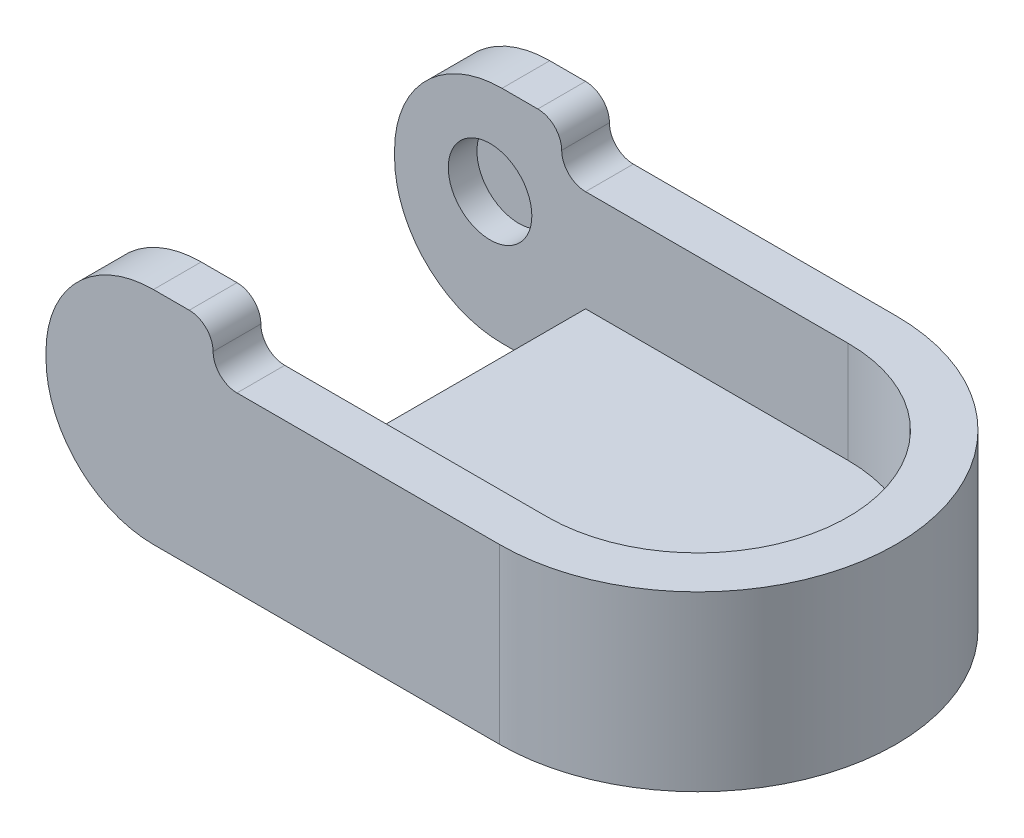
SolidWorks part; units mm, degrees
ref_plane "Front Plane" through (0, 0, 0) normal (0, 0, 1) x (1, 0, 0)
ref_plane "Top Plane" through (0, 0, 0) normal (0, 1, 0) x (1, 0, 0)
ref_plane "Right Plane" through (0, 0, 0) normal (1, 0, 0) x (0, 0, -1)
sketch "Sketch1" plane through (0, 0, 0) normal (0, 1, 0) x (1, 0, 0)
  line L0 (0, 0) -> (17, 0)
  line L1 (17, 16.6) -> (0, 16.6)
  line L2 (0, 16.6) -> (0, 14.6)
  line L3 (0, 14.6) -> (6, 14.6)
  line L4 (6, 14.6) -> (6, 2)
  line L5 (6, 2) -> (0, 2)
  line L6 (0, 2) -> (0, 0)
  arc A0 (17, 0) -> (17, 16.6) centre (17, 8.3) ccw
  dimension "D1" = 8.3
  dimension "D2" = 17
  dimension "D3" = 2
  dimension "D4" = 2
  dimension "D5" = 6
extrude "Boss-Extrude1" add sketch "Sketch1" along normal blind 3
sketch "Sketch2" plane through (0, 3, 0) normal (0, 1, 0) x (1, 0, 0)
  line L0 (0, 2) -> (17, 2)
  line L1 (17, 14.6) -> (0, 14.6)
  line L7 (0, 2) -> (0, 0)
  line L8 (0, 0) -> (17, 0)
  line L9 (17, 16.6) -> (0, 16.6)
  line L10 (0, 16.6) -> (0, 14.6)
  line L11 (0, 14.6) -> (6, 14.6)
  line L12 (6, 14.6) -> (6, 2)
  line L13 (6, 2) -> (0, 2)
  line L14 (0, 2) -> (0, 0)
  line L15 (0, 0) -> (17, 0)
  line L16 (17, 16.6) -> (0, 16.6)
  line L17 (0, 16.6) -> (0, 14.6)
  line L18 (0, 14.6) -> (6, 14.6)
  line L19 (6, 14.6) -> (6, 2)
  line L20 (6, 2) -> (0, 2)
  arc A0 (17, 2) -> (17, 14.6) centre (17, 8.3) ccw
  arc A1 (17, 0) -> (17, 16.6) centre (17, 8.3) ccw
  arc A2 (17, 0) -> (17, 16.6) centre (17, 8.3) ccw
  line M9 (0, 2) -> (0, 0)
  line M10 (0, 0) -> (17, 0)
  arc M11 (17, 0) -> (17, 16.6) centre (17, 8.3) ccw
  line M12 (17, 16.6) -> (0, 16.6)
  line M13 (0, 16.6) -> (0, 14.6)
  line M14 (0, 14.6) -> (6, 14.6)
  line M16 (6, 2) -> (0, 2)
  dimension "D1" = 0
  dimension "D2" = 2
extrude "Boss-Extrude2" add sketch "Sketch2" along normal blind 4.25 contours A0 L0 L1 M16 M9 M10 M11 M12 M13 M14 region at (3, 3, -1.6974)
sketch "Sketch3" plane through (0, 0, -14.6) normal (0, 0, 1) x (1, 0, 0)
  line L0 (4, 3.25) -> (0, 7.25) construction
  line L1 (0, 7.25) -> (4, 7.25)
  line L2 (0, 7.25) -> (0, 3.25)
  line L3 (0, 3.25) -> (4, 3.25)
  line L4 (4, 7.25) -> (4, 3.25)
  circle A0 centre (2, 5.25) radius 1.75
  dimension "D3" = 3.5
  dimension "D1" = 4
  dimension "D2" = 4
extrude "Cut-Extrude1" cut sketch "Sketch3" against normal blind 1.2 contours A0 L0 | L0 A0 region at (1.4748, 4.7248, -14.6) region at (2.5252, 5.7752, -14.6)
sketch "Sketch4" plane through (0, 0, -2) normal (0, 0, -1) x (-1, 0, 0)
  line L0 (0, 7.25) -> (-4, 3.25) construction
  line L1 (0, 7.25) -> (-4, 7.25)
  line L2 (0, 7.25) -> (0, 3.25)
  line L3 (0, 3.25) -> (-4, 3.25)
  line L4 (-4, 7.25) -> (-4, 3.25)
  circle A0 centre (-2, 5.25) radius 1.75
  dimension "D3" = 3.5
  dimension "D1" = 4
  dimension "D2" = 4
extrude "Cut-Extrude2" cut sketch "Sketch4" against normal blind 1.2 contours L0 A0 | A0 L0 | A0 region at (1.4748, 4.7248, -2) region at (2.5252, 5.7752, -2)
sketch "Sketch5" plane through (0, 0, 0) normal (0, 0, 1) x (1, 0, 0)
  line L0 (5, 7.25) -> (5, 9.25)
  line L1 (0, 7.25) -> (17, 7.25) construction
  line L2 (5, 9.25) -> (-2, 9.25)
  line L3 (-2, 9.25) -> (-2, 0)
  line L4 (-2, 0) -> (0, 0)
  line L5 (0, 7.25) -> (0, 0) construction
  line L6 (0, 0) -> (0, 7.25)
  line L7 (0, 7.25) -> (5, 7.25)
  dimension "D1" = 2
  dimension "D2" = 2
  dimension "D3" = 5
extrude "Boss-Extrude3" add sketch "Sketch5" against normal blind 2
sketch "Sketch6" plane through (0, 0, -16.6) normal (0, 0, -1) x (-1, 0, 0)
  line L0 (-5, 7.25) -> (-5, 9.25)
  line L1 (-5, 9.25) -> (2, 9.25) construction
  line L2 (-5, 9.25) -> (2, 9.25)
  line L3 (2, 9.25) -> (2, 0)
  line L4 (2, 0) -> (0, 0)
  line L5 (0, 0) -> (0, 7.25)
  line L6 (0, 7.25) -> (0, 0) construction
  line L7 (-17, 7.25) -> (0, 7.25) construction
  line L8 (0, 7.25) -> (-5, 7.25)
extrude "Boss-Extrude4" add sketch "Sketch6" against normal blind 2
fillet "Fillet2" radius 4.5 4 edges at (-2, 0, -1) (-2, 0, -15.6) (-2, 9.25, -1) (-2, 9.25, -15.6)
fillet "Fillet3" radius 1 4 edges at (5, 7.25, -15.6) (5, 9.25, -15.6) (5, 7.25, -1) (5, 9.25, -1)
ref_plane "Plane1" through (23.5, 0, 0) normal (1, 0, 0) x (0, 0, -1)
sketch "Sketch7" plane through (23.5, 0, 0) normal (1, 0, 0) x (0, 0, -1)
  line L0 (14.6, 7.25) -> (2, 3) construction
  line L2 (5.8, 4.575) -> (10.8, 4.575)
  line L3 (5.8, 4.575) -> (5.8, 5.675)
  line L4 (5.8, 5.675) -> (10.8, 5.675)
  line L5 (10.8, 4.575) -> (10.8, 5.675)
  line L6 (5.8, 4.575) -> (10.8, 5.675) construction
  line L7 (5.8, 5.675) -> (10.8, 4.575) construction
  point P4 (8.3, 5.125)
  dimension "D1" = 5
  dimension "D2" = 1.1
extrude "Boss-Extrude5" add sketch "Sketch7" against normal blind 0.7
fillet "Fillet4" radius 0.5 2 edges at (22.8, 4.575, -8.3) (22.8, 5.675, -8.3)
